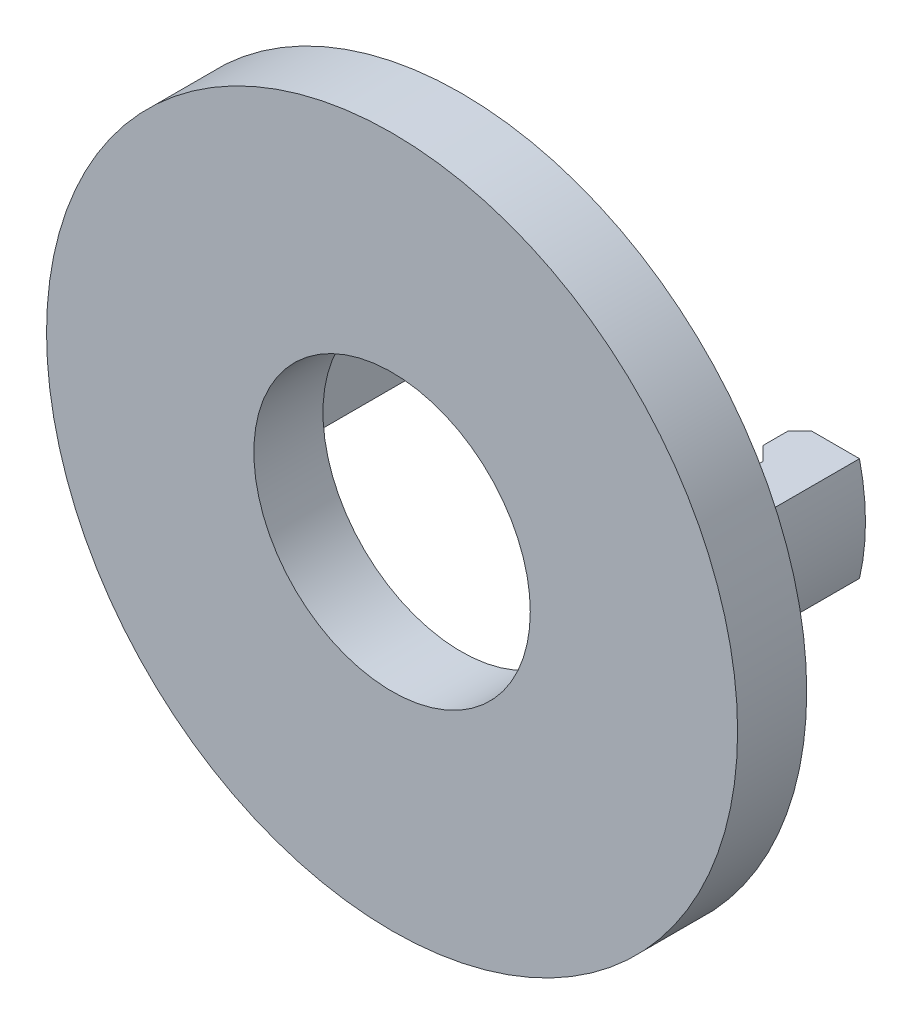
SolidWorks part; units mm, degrees
ref_plane "Front" through (0, 0, 0) normal (0, 0, 1) x (1, 0, 0)
ref_plane "Top" through (0, 0, 0) normal (0, 1, 0) x (1, 0, 0)
ref_plane "Right" through (0, 0, 0) normal (1, 0, 0) x (0, 0, -1)
sketch "Guard base" plane through (0, 0, 0) normal (0, 0, 1) x (1, 0, 0)
  circle A0 centre (0, 0) radius 25
  dimension "D1" = 50
extrude "Guard" add sketch "Guard base" along normal blind 5
sketch "Inner axle hole base" plane through (0, 0, 5) normal (0, 0, 1) x (1, 0, 0)
  circle A0 centre (0, 0) radius 10
  dimension "D1" = 20
extrude "Inner axle hole" cut sketch "Inner axle hole base" against normal through all
sketch "Coupling tooth base" plane through (0, 0, 0) normal (0, 1, 0) x (1, 0, 0)
  line L0 (10, 0) -> (15.5, 0) construction
  line L1 (15.5, 0) -> (15.5, 13)
  line L2 (12.5, 2.5) -> (12.5, 9) construction
  line L3 (15.5, 13) -> (12.5, 13) construction
  line L4 (12.5, 13) -> (11.5, 12) construction
  line L5 (11.5, 10) -> (12.5, 9) construction
  line L6 (16.5, 12.75) -> (16.5, 0)
  line L7 (12.75, 9.1036) -> (12.75, 2.3964)
  line L8 (12.5, 2.5) -> (10, 0) construction
  line L9 (12.75, 9.1036) -> (11.75, 10.1036)
  line L10 (11.5, 12) -> (11.5, 10) construction
  line L11 (11.75, 10.1036) -> (11.75, 11.8964)
  line L12 (15.5, 0) -> (15.5, 12.75) construction
  line L13 (15.5, 0) -> (10.3536, 0)
  line L14 (12.75, 2.3964) -> (10.3536, 0)
  line L15 (11.75, 11.8964) -> (12.6036, 12.75)
  line L16 (12.6036, 12.75) -> (15.5, 12.75)
  line L17 (15.5, 12.75) -> (25, 12.75)
  line L18 (25, 12.75) -> (25, 0)
  line L19 (25, 0) -> (15.5, 0)
  dimension "D2" = 1
  dimension "D3" = 4
  dimension "D4" = 13
  dimension "D5" = 4
  dimension "D6" = 0.25
  dimension "D7" = 0.25
  dimension "D8" = 0.25
  dimension "D9" = 0.25
  dimension "D10" = 225
  dimension "D11" = 5.5
  dimension "D12" = 0.25
  dimension "D13" = 135
  dimension "D14" = 0.25
  dimension "D15" = 1
extrude "Coupling tooth" add sketch "Coupling tooth base" along normal blind 3.75 and the other way blind 3.75 contours L16 L15 L11 L9 L7 L14 L13 L1 | L19 L6 L17 L1 region at (13.8475, 0, -6.2973) region at (16, 0, -6.375)
ref_axis "Center Z" through (0, 0, 0) along (0, 0, -1)
revolve "Circularity cut" cut sketch "Sketch6<4>" angle 360 about axis through (0, 0, 0) along (0, 0, -1) region at (20.75, 0, -6.375)
sketch "Sketch6<4>" plane through (0, 0, 0) normal (0, 1, 0) x (1, 0, 0) same geometry as "Coupling tooth base"
mirror "Coutpling teeth" about plane through (0, 0, 0) normal (1, 0, 0) of "Coupling tooth", "Circularity cut"
equation "\"mate_room\"= 0.25"
equation "\"D6@Coupling tooth base\"=\"mate_room\""
equation "\"D8@Coupling tooth base\"=\"mate_room\""
equation "\"D7@Coupling tooth base\"=\"mate_room\""
equation "\"D9@Coupling tooth base\"=\"mate_room\""
equation "\"D12@Coupling tooth base\"=\"mate_room\""
equation "\"D14@Coupling tooth base\"=\"mate_room\""
equation "\"removal_room\"= 0.75"
equation "\"large_inner_axle_diameter\"=20"
equation "\"D1@Inner axle hole base\"=\"large_inner_axle_diameter\""
equation "\"guard_thickness\"=5"
equation "\"spool_inner_diameter_room\"=1"
equation "\"32_92_coupling_tooth_height\"=13"
equation "\"32_92_coupling_tooth_thickness_total\"=4"
equation "\"32_92_coupling_tooth_protrusion\"=1"
equation "\"32_92_coupling_tooth_depth\"=8"
equation "\"32_92_coupling_tooth_base_thickness\"=5.5"
equation "\"D1@Guard\"=\"guard_thickness\""
equation "\"32_92_guard_diameter\"=50"
equation "\"D1@Guard base\"=\"32_92_guard_diameter\""
equation "\"D4@Coupling tooth base\"=\"32_92_coupling_tooth_height\""
equation "\"D3@Coupling tooth base\"=\"32_92_coupling_tooth_thickness_total\""
equation "\"D2@Coupling tooth base\"=\"32_92_coupling_tooth_protrusion\""
equation "\"D11@Coupling tooth base\"=\"32_92_coupling_tooth_base_thickness\""
equation "\"32_92_coupling_tooth_head_height\"=4"
equation "\"D5@Coupling tooth base\"=\"32_92_coupling_tooth_head_height\""
equation "\"32_92_spool_inner_diameter\"=32"
equation "\"32_92_spool_thickness\"=92"
